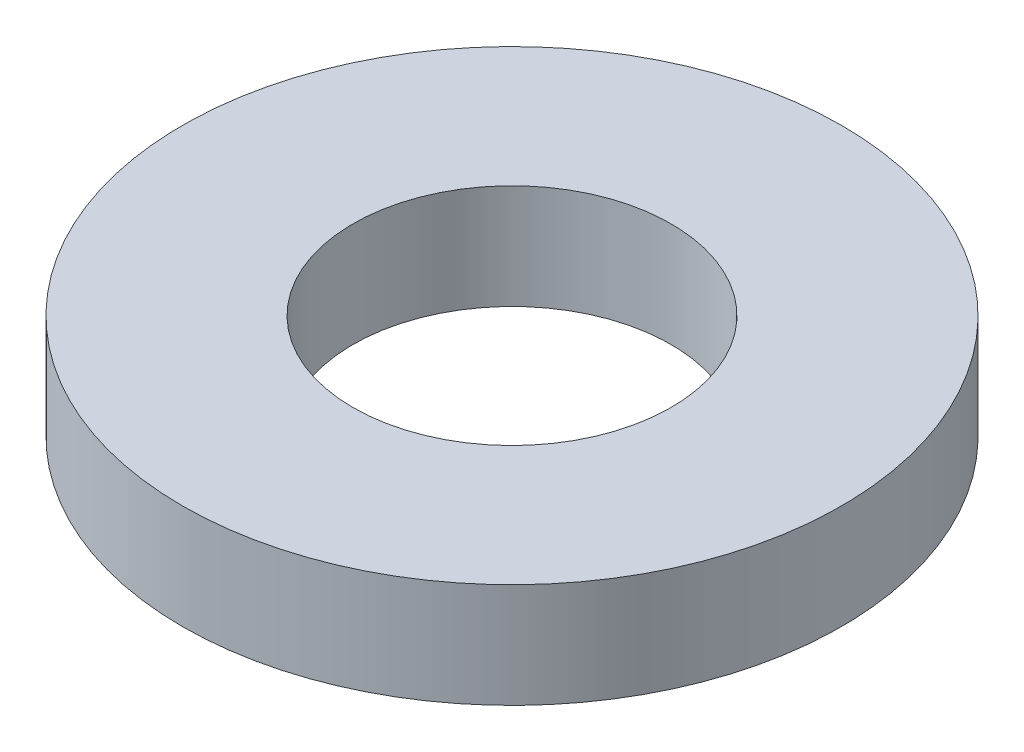
SolidWorks part; units mm, degrees
ref_plane "Front Plane" through (0, 0, 0) normal (0, 0, 1) x (1, 0, 0)
ref_plane "Top Plane" through (0, 0, 0) normal (0, 1, 0) x (1, 0, 0)
ref_plane "Right Plane" through (0, 0, 0) normal (1, 0, 0) x (0, 0, -1)
sketch "Sketch1" plane through (0, 0, 0) normal (0, 1, 0) x (1, 0, 0)
  circle A0 centre (0, 0) radius 72.5
  dimension "FLANGE_OD" = 145
extrude "Boss-Extrude1" add sketch "Sketch1" along normal blind 23
sketch "Sketch2" plane through (0, 0, 0) normal (0, 1, 0) x (1, 0, 0)
  circle A0 centre (0, 0) radius 35
  dimension "BORE_D" = 70
extrude "Cut-Extrude1" cut sketch "Sketch2" along normal through all
sketch "Sketch3" plane through (0, 23, 0) normal (0, 1, 0) x (1, 0, 0)
  circle A0 centre (0, 0) radius 23.3057 construction
  circle A1 centre (-23.3057, 0) radius 5.1111
  dimension "BOLT_D" = 10.2222
  dimension "BOLT_PCD" = 46.6113
extrude "Cut-Extrude2" cut sketch "Sketch3" against normal blind 22.3494 rebuild error yes
pattern_circular "CirPattern1" count 5 over 360 rebuild error yes
